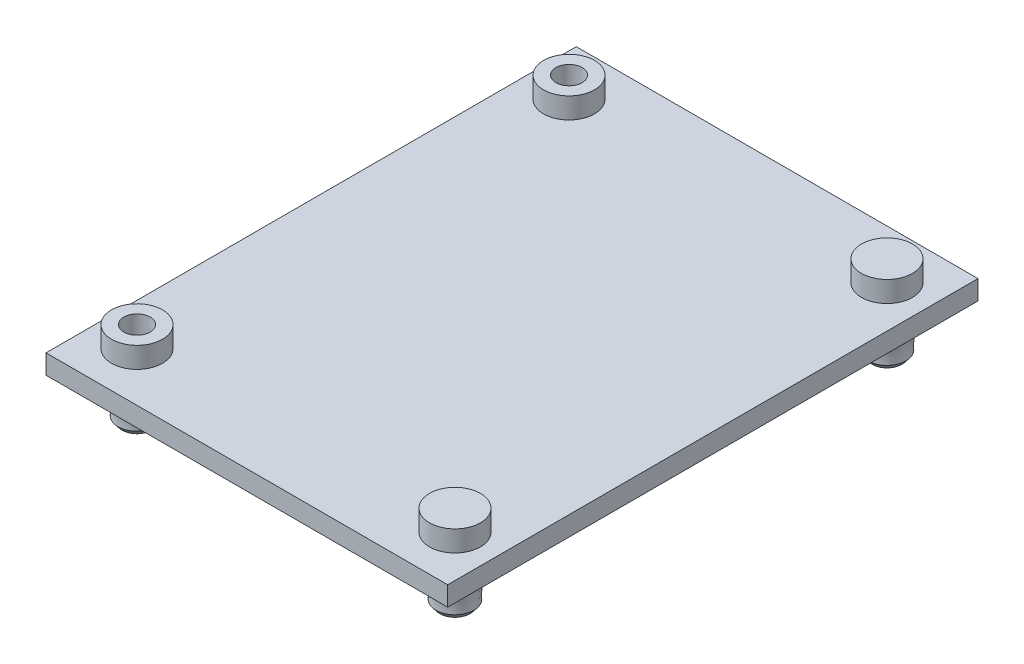
SolidWorks part; units mm, degrees
material "ABS"
ref_plane "Piano frontale" through (0, 0, 0) normal (0, 0, 1) x (1, 0, 0)
ref_plane "Piano superiore" through (0, 0, 0) normal (0, 1, 0) x (1, 0, 0)
ref_plane "Piano destro" through (0, 0, 0) normal (1, 0, 0) x (0, 0, -1)
sketch "Schizzo1" plane through (0, 0, 0) normal (0, 1, 0) x (1, 0, 0)
  line L0 (-45.875, -54.625) -> (45.875, 54.625) construction
  line L5 (45.875, -54.625) -> (-45.875, 54.625) construction
  line L7 (-45.875, 54.625) -> (45.875, 54.625)
  line L8 (-45.875, 54.625) -> (-45.875, -54.625)
  line L9 (-45.875, -54.625) -> (45.875, -54.625)
  line L11 (36.875, -54.625) -> (36.875, 54.625)
  line L12 (-37.25, 44.5) -> (37.25, 44.5) construction
  line L13 (-37.25, 44.5) -> (-37.25, -44.5) construction
  line L14 (-37.25, -44.5) -> (37.25, -44.5) construction
  line L15 (37.25, 44.5) -> (37.25, -44.5) construction
  circle A8 centre (-37.25, 44.5) radius 2.25 construction
  circle A9 centre (37.25, 44.5) radius 2.25 construction
  circle A10 centre (37.25, -44.5) radius 2.25 construction
  circle A11 centre (-37.25, -44.5) radius 2.25 construction
  point P4 (0, 0)
  point P16 (0, 0)
  point P17 (0, 0)
  dimension "D1" = 4.5
  dimension "D2" = 109.25
  dimension "D3" = 91.75
  dimension "D4" = 74.5
  dimension "D5" = 89
  dimension "D6" = 44.5
  dimension "D7" = 37.25
  dimension "D8" = 9
  dimension "D9" = 9
extrude "Estrusione-Estrusione2" add sketch "Schizzo1" along normal blind 4 contours L9 L11 L7 L8 region at (-4.5, 0, 0)
ref_plane "Piano1" through (0, -9, 0) normal (0, -1, 0) x (-1, 0, 0)
sketch "Schizzo3" plane through (0, 4, 0) normal (0, 1, 0) x (1, 0, 0)
  line L0 (28.25, 44.5) -> (28.25, -44.5) construction
  line L1 (28.25, -44.5) -> (-37.25, -44.5) construction
  line L2 (-37.25, 44.5) -> (28.25, 44.5) construction
  circle A1 centre (-37.25, -44.5) radius 5.25
  circle A3 centre (-37.25, 44.5) radius 5.25
  circle A5 centre (28.25, -44.5) radius 5.25
  circle A6 centre (28.25, 44.5) radius 5.25
  dimension "D1" = 10.5
  dimension "D2" = 65.5
extrude "Estrusione-Estrusione3" add sketch "Schizzo3" along normal blind 4.3
sketch "Schizzo4" plane through (0, 0, 0) normal (0, -1, 0) x (1, 0, 0)
  circle A0 centre (-37.25, 44.5) radius 5.25
  dimension "D1" = 10.5
sketch "Schizzo5" plane through (0, -9, 0) normal (0, -1, 0) x (-1, 0, 0)
  circle A4 centre (37.25, -44.5) radius 4
  dimension "D2" = 8
loft "Loft1" add profiles "Schizzo4", "Schizzo5" connector at (-42.4246, 0, 43.6136) connector at (-40.0028, -9, 47.4021)
pattern_linear "Ripetizione a L1" count 2 spacing 65.5 along (1, 0, 0) count 2 spacing 89 along (0, 0, -1) of "Loft1"
chamfer "Smusso1" distance 1 angle 45 4 edges at (-37.25, -9, 40.5) (28.25, -9, 40.5) (28.25, -9, -48.5) (-37.25, -9, -48.5) first distance on face at (-37.25, 0, 39.25) first distance on face at (28.25, 0, 39.25) first distance on face at (28.25, 0, -49.75) first distance on face at (-37.25, 0, -49.75)
sketch "Schizzo6" plane through (0, 8.3, 0) normal (0, 1, 0) x (1, 0, 0)
  point P0 (-37.25, 44.5)
  point P9 (-37.25, -44.5)
  point P13 (0, 0)
  point P14 (0, 0)
hole_wizard "Foro per Vite M3-1" positions "Schizzo6" profile "Schizzo7" hole size "M3" standard "ISO"
sketch "Schizzo7" plane through (-37.25, 8.3, -44.5) normal (1, 0, 0) x (0, 0, 1)
  line L0 (0, 0) -> (0, 11.6223)
  line L1 (0, 11.6223) -> (2.7, 10)
  line L2 (2.7, 10) -> (2.7, 0)
  line L5 (2.7, 0) -> (0, 0)
  line L10 (0, 11.6223) -> (-2.7, 10) construction
  line L11 (0, -6.35) -> (0, 107.95) construction
  dimension "Hole Dia." = 5.4
  dimension "Hole Depth" = 10
  dimension "Drill Angle" = 118
